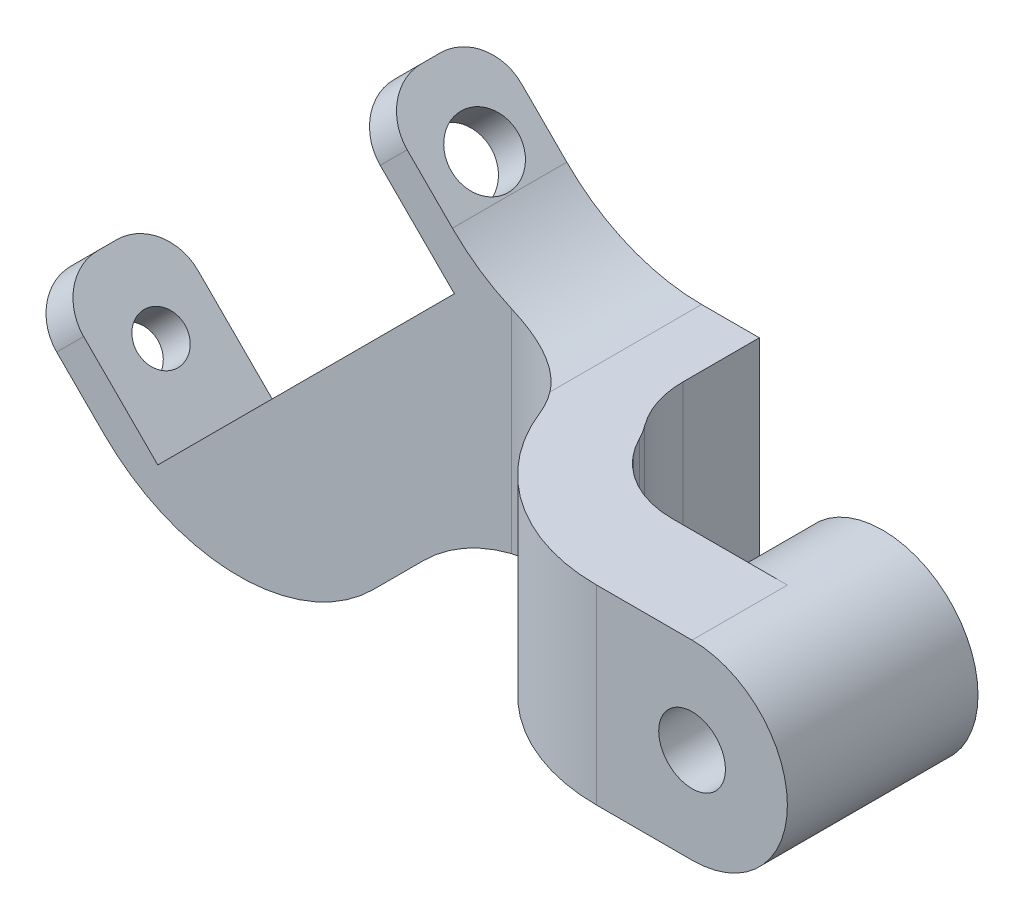
SolidWorks part; units mm, degrees
material "PET"
ref_plane "Piano frontale" through (0, 0, 0) normal (0, 0, 1) x (1, 0, 0)
ref_plane "Piano superiore" through (0, 0, 0) normal (0, 1, 0) x (1, 0, 0)
ref_plane "Piano destro" through (0, 0, 0) normal (1, 0, 0) x (0, 0, -1)
sketch "Schizzo1" plane through (0, 0, 0) normal (0, 0, 1) x (1, 0, 0)
  line L0 (0, 0) -> (-20, 0)
  line L1 (-20, 0) -> (-10, 10)
  line L2 (-10, 10) -> (10, 10)
  line L4 (10, 0) -> (0, 0)
  arc A0 (10, 0) -> (10, 10) centre (10, 5) ccw
  dimension "D6" = 10
  dimension "D1" = 20
  dimension "D2" = 10
  dimension "D3" = 10
  dimension "D4" = 0
  dimension "D5" = 20
extrude "Estrusione-Estrusione1" add sketch "Schizzo1" along normal blind 6 contours L2 A0 L4 L0 L1
sketch "Schizzo3" plane through (0, 0, 6) normal (0, 0, 1) x (1, 0, 0)
  arc A0 (10, 0) -> (10, 10) centre (10, 5) ccw construction
  arc A1 (10, 0) -> (10, 10) centre (10, 5) ccw construction
  circle A2 centre (10, 5) radius 5
  circle A3 centre (10, 5) radius 2.65
  dimension "D1" = 5.3
extrude "Estrusione-Estrusione3" add sketch "Schizzo3" against normal blind 11
sketch "Schizzo4" plane through (0, 0, 6) normal (0, 0, 1) x (1, 0, 0)
  line L0 (-10, 10) -> (-16.0795, 16.0795)
  line L1 (-20, 0) -> (-10, 10) construction
ref_plane "Piano1" through (0, 0, 0) normal (0.7071, 0.7071, 0) x (-0.7071, 0.7071, 0)
sketch "Schizzo5" plane through (0, 0, 0) normal (0.7071, 0.7071, 0) x (-0.7071, 0.7071, 0)
  line L0 (14.1421, 3) -> (18.1421, 3)
  line L1 (14.1421, 6) -> (14.1421, 0) construction
  circle A0 centre (18.1421, 3) radius 0.925
  dimension "D2" = 1.85
  dimension "D1" = 4
extrude "Estrusione-Estrusione4" add sketch "Schizzo5" against normal blind 20 separate body contours A0 region at (-12.8284, 12.8284, 2.1012)
sketch "Schizzo12" plane through (0, 0, 0) normal (0.7071, 0.7071, 0) x (-0.7071, 0.7071, 0)
  line L0 (14.1421, 0) -> (0, 0) construction
  line L1 (14.1421, 6) -> (22.1421, 6)
  line L2 (14.1421, 6) -> (14.1421, 0)
  line L3 (14.1421, 0) -> (22.1421, 0)
  line L4 (22.1421, 6) -> (22.1421, 0)
  dimension "D1" = 8
extrude "Estrusione-Estrusione6" add sketch "Schizzo12" along normal blind 2
sketch "Schizzo13" plane through (-10, 10, 0) normal (0.7071, -0.7071, 0) x (0, 0, -1)
  line L4 (-6, 0) -> (0, 0)
  line L5 (0, 0) -> (0, 2)
  line L6 (0, 2) -> (-6, 2)
  line L7 (-6, 2) -> (-6, 0)
  line L8 (-6, 0) -> (0, 0)
  line L9 (0, 0) -> (0, 2)
  line L10 (0, 2) -> (-6, 2)
  line L11 (-6, 2) -> (-6, 0)
  dimension "D1" = 0
extrude "Estrusione-Estrusione7" add sketch "Schizzo13" along normal blind 3
fillet "Raccordo2" radius 2.5 2 edges at (-14.9497, 16.364, 0) (-14.9497, 16.364, 6)
sketch "Schizzo14" plane through (1.4142, 1.4142, 0) normal (0.7071, 0.7071, 0) x (0, 0, -1)
  circle A0 centre (-3, 18.1421) radius 1.75
  circle A1 centre (-3, 18.1421) radius 0.925
  circle A2 centre (-3, 18.1421) radius 0.925
  dimension "D2" = 3.5
  dimension "D1" = 0
extrude "Taglio-Estrusione7" cut sketch "Schizzo14" against normal blind 25 contours A2 | A0 A2 | A2 | A0 region at (-11.4142, 14.2426, 4.7005) region at (-11.4142, 14.2426, 3)
sketch "Schizzo15" plane through (0, 0, 0) normal (-0.7071, -0.7071, 0) x (0, 0, 1)
  line L0 (0, 14.1421) -> (0, 19.6421) construction
  line L1 (6, 14.1421) -> (0, 14.1421)
  line L2 (6, 14.1421) -> (6, 6.1421)
  line L3 (6, 6.1421) -> (0, 6.1421)
  line L4 (0, 14.1421) -> (0, 6.1421)
  dimension "D1" = 8
extrude "Estrusione-Estrusione8" add sketch "Schizzo15" along normal blind 24
sketch "Schizzo16" plane through (-10, 10, 0) normal (-0.7071, 0.7071, 0) x (0, 0, 1)
  line L0 (0, -24) -> (0, 0) construction
  line L1 (6, -24) -> (0, -24)
  line L2 (6, -24) -> (6, -22)
  line L3 (6, -22) -> (0, -22)
  line L4 (0, -24) -> (0, -22)
  dimension "D1" = 2
extrude "Estrusione-Estrusione9" add sketch "Schizzo16" along normal up to vertex (8 mm away) up to point (-15.6569, 15.6569, 2.5)
sketch "Schizzo17" plane through (-16.9706, -16.9706, 0) normal (-0.7071, -0.7071, 0) x (0, 0, 1)
  circle A0 centre (3, 18.1421) radius 1.75 construction
  circle A1 centre (3, 18.1421) radius 1.75
  circle A2 centre (3, 18.1421) radius 1.25
  dimension "D1" = 2.5
extrude "Taglio-Estrusione8" cut sketch "Schizzo17" against normal blind 25 contours A2
fillet "Raccordo3" radius 10 1 edges at (-21.3137, -12.6274, 3)
fillet "Raccordo4" radius 10 1 edges at (-8.6863, 0, 3)
fillet "Raccordo5" radius 10 1 edges at (-7.1716, 10, 3)
fillet "Raccordo6" radius 2.5 2 edges at (-31.9203, -0.6066, 0) (-31.9203, -0.6066, 6)
sketch "Schizzo18" plane through (0, 0, 6) normal (0, 0, 1) x (1, 0, 0)
  circle A0 centre (10, 5) radius 1.75
  dimension "D1" = 3.5
extrude "Taglio-Estrusione9" cut sketch "Schizzo18" against normal through all
ref_axis "Assi1" through (-14.0659, 11.591, 3) along (0.7071, 0.7071, 0)
ref_axis "Assi2" through (-13.8891, 13.8891, 6) along (0.7071, -0.7071, 0)
ref_axis "Assi3" through (-10.1005, 12.9289, 6) along (0, 0, -1)
ref_point "Punto1"
ref_point "Punto2"
ref_axis "Assi4" through (10, 5, 0) along (0, 0, -1)
ref_axis "Assi5" through (-3.0294, 10, 6) along (1, 0, 0)
ref_point "Punto3"
sketch "Schizzo19" plane through (0, 0, 0) normal (0, 0, -1) x (-1, 0, 0)
  line L0 (-10, 5) -> (19.95, 5)
  dimension "D1" = 29.95
sketch "Schizzo20" plane through (0, 0, -5) normal (0, 0, -1) x (-1, 0, 0)
  line L1 (-20, 14.6545) -> (0, 14.6545)
  line L2 (-20, 14.6545) -> (-20, -4.6545)
  line L3 (-20, -4.6545) -> (0, -4.6545)
  line L4 (0, 14.6545) -> (0, -4.6545)
  line L5 (-20, 14.6545) -> (0, -4.6545) construction
  line L6 (-20, -4.6545) -> (0, 14.6545) construction
  point P0 (-10, 5)
  point P5 (0, 0)
  dimension "D1" = 20
extrude "Taglio-Estrusione10" cut sketch "Schizzo20" against normal through all
sketch "Schizzo21" plane through (0, 0, 6) normal (0, 0, 1) x (1, 0, 0)
  line L1 (-3.0294, 10) -> (1.9706, 10)
  line L2 (-3.0294, 10) -> (-3.0294, 0)
  line L3 (-3.0294, 0) -> (1.9706, 0)
  line L4 (1.9706, 10) -> (1.9706, 0)
  dimension "D1" = 5
extrude "Estrusione-Estrusione10" add sketch "Schizzo21" along normal blind 9.5
sketch "Schizzo22" plane through (1.9706, 0, 0) normal (1, 0, 0) x (0, 0, -1)
  line L0 (-15.5, 0) -> (-6, 0) construction
  line L1 (-15.5, 10) -> (-10.5, 10)
  line L2 (-15.5, 10) -> (-15.5, 0)
  line L3 (-15.5, 0) -> (-10.5, 0)
  line L4 (-10.5, 10) -> (-10.5, 0)
  dimension "D1" = 5
extrude "Estrusione-Estrusione11" add sketch "Schizzo22" along normal blind 15
sketch "Schizzo24" plane through (0, 0, 10.5) normal (0, 0, -1) x (-1, 0, 0)
  line L0 (-16.9706, 5) -> (-11.9706, 5)
  line L1 (-16.9706, 0) -> (-16.9706, 10) construction
  circle A0 centre (-11.9706, 5) radius 5
  circle A1 centre (-11.9706, 5) radius 2.6
  point P4 (0, 0)
  dimension "D1" = 10
  dimension "D2" = 5.2
  dimension "D3" = 5
fillet "Raccordo7" radius 5 3 edges at (1.9706, 5, 6) (16.9706, 0, 13) (16.9706, 10, 13)
fillet "Raccordo8" radius 10 1 edges at (-3.0294, 5, 15.5)
fillet "Raccordo9" radius 5 1 edges at (-3.0294, 5, 6)
extrude "Estrusione-Estrusione13" add sketch "Schizzo24" along normal blind 5 contours A1 A0 region at (11.9706, 9.8586, 10.5)
sketch "Schizzo26" plane through (0, 0, 10.5) normal (0, 0, -1) x (-1, 0, 0)
  circle A0 centre (-11.9706, 5) radius 1.75
  dimension "D1" = 3.5
extrude "Taglio-Estrusione12" cut sketch "Schizzo26" against normal through all
fillet "Raccordo10" radius 5 2 edges at (0, 5, 6) (1.9706, 5, 10.5)
sketch "Schizzo27" plane through (0, 0, 0) normal (0, 0, -1) x (-1, 0, 0)
  line L0 (-10, 5) -> (-11.9706, 5)
